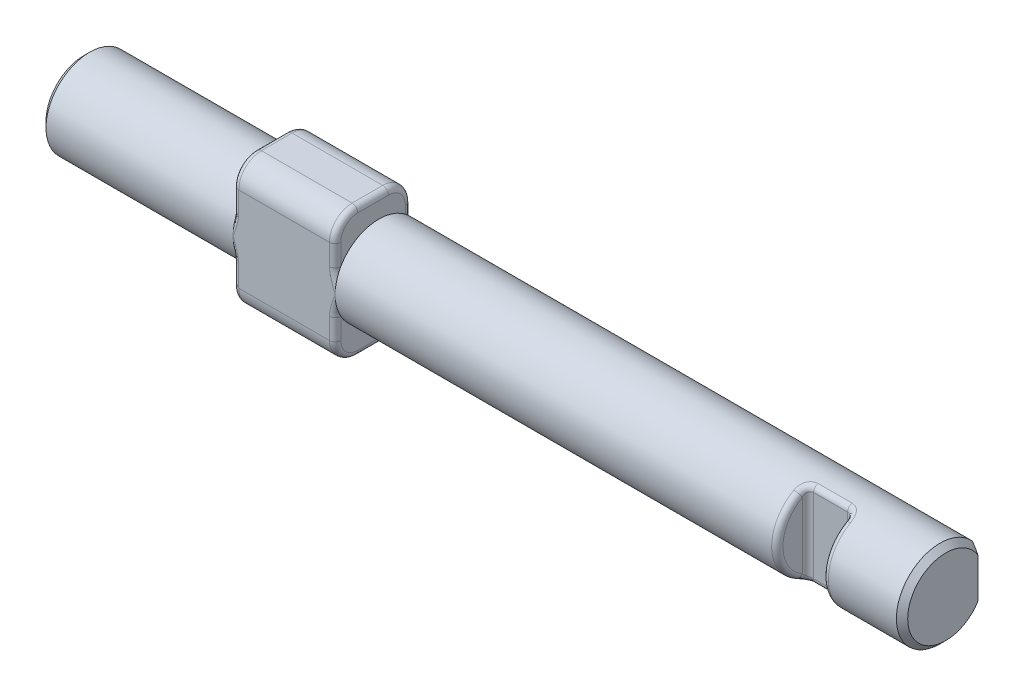
SolidWorks part; units mm, degrees
ref_plane "Front Plane" through (0, 0, 0) normal (0, 0, 1) x (1, 0, 0)
ref_plane "Top Plane" through (0, 0, 0) normal (0, 1, 0) x (1, 0, 0)
ref_plane "Right Plane" through (0, 0, 0) normal (1, 0, 0) x (0, 0, -1)
sketch "Sketch1" plane through (0, 0, 0) normal (1, 0, 0) x (0, 0, -1)
  line L0 (-1, -2.5884) -> (-1, 2.5884)
  circle A0 centre (-3.85, 0) radius 3.85
  point P4 (0, 0)
  dimension "D1" = 7.7
  dimension "D2" = 1
extrude "Boss-Extrude1" add sketch "Sketch1" along normal blind 76 contours L0 A0 region at (0, 0, 4.1188)
sketch "Sketch2" plane through (0, 0, 0) normal (-1, 0, 0) x (0, 0, 1)
  line L0 (1, -2.5884) -> (1, 2.5884) construction
  line L1 (1, -4.0731) -> (1, 4.0731) construction
  line L2 (4.35, 0) -> (0, 0) construction
  line L3 (7.7, 5.75) -> (1, 5.75)
  line L4 (7.7, 5.75) -> (7.7, -5.75)
  line L5 (7.7, -5.75) -> (1, -5.75)
  line L6 (1, 5.75) -> (1, -5.75)
  line L7 (7.7, 5.75) -> (1, -5.75) construction
  line L8 (7.7, -5.75) -> (1, 5.75) construction
  arc A1 (1, -2.5884) -> (1, 2.5884) centre (3.85, 0) ccw construction
  point P7 (4.35, 0)
  dimension "D1" = 11.5
extrude "Boss-Extrude2" add sketch "Sketch2" along normal blind 9 from offset 26 contours L1 | L3 L6 L5 L4 region at (0, 0, 4.35) offset against normal yes
fillet "Fillet1" radius 0.5 rebuild error yes
chamfer "Chamfer1" distance 0.5 angle 45 2 edges at (0, 0, 7.7) (76, 0, 7.7)
sketch "Sketch3" plane through (0, 0, 1) normal (0, 0, -1) x (-1, 0, 0)
  line L1 (-69, 1.7607) -> (-69, 5)
  line L2 (-69, -1.7607) -> (-69, 1.7607)
  line L3 (-69, -1.7607) -> (-69, 1.7607)
  line L4 (-69, 5) -> (-65, 5)
  line L5 (-65, 5) -> (-65, -5)
  line L6 (-65, -5) -> (-69, -5)
  line L7 (-69, -5) -> (-69, -1.7607)
  dimension "D2" = 10
  dimension "D3" = 4
  dimension "D1" = 7
extrude "Cut-Extrude1" cut sketch "Sketch3" against normal through all from offset 4 offset against normal yes
fillet "Fillet2" radius 0.5 6 edges at (67, 3.6742, 5) (67, -3.6742, 5) (65, 0, 7.7) (65, 0, 5) (69, 0, 7.7) (69, 0, 5)
fillet "Fillet3" radius 2 4 edges at (21.5, -5.75, 1) (21.5, 5.75, 1) (21.5, -5.75, 7.7) (21.5, 5.75, 7.7)
fillet "Fillet4" radius 0.5 20 edges at (26, 3.1692, 1) (26, 5.1642, 1.5858) (26, 5.75, 4.35) (26, 5.1642, 7.1142) (26, 1.875, 7.7) (26, -1.875, 7.7) (26, -3.1692, 1) (26, -5.1642, 1.5858) (26, -5.75, 4.35) (17, -3.1692, 1) (17, -5.1642, 1.5858) (17, -5.75, 4.35) (17, 3.1692, 1) (17, 5.1642, 1.5858) (17, 5.75, 4.35) (17, 5.1642, 7.1142) (17, 1.875, 7.7) (17, -1.875, 7.7) (26, -5.1642, 7.1142) (17, -5.1642, 7.1142)
